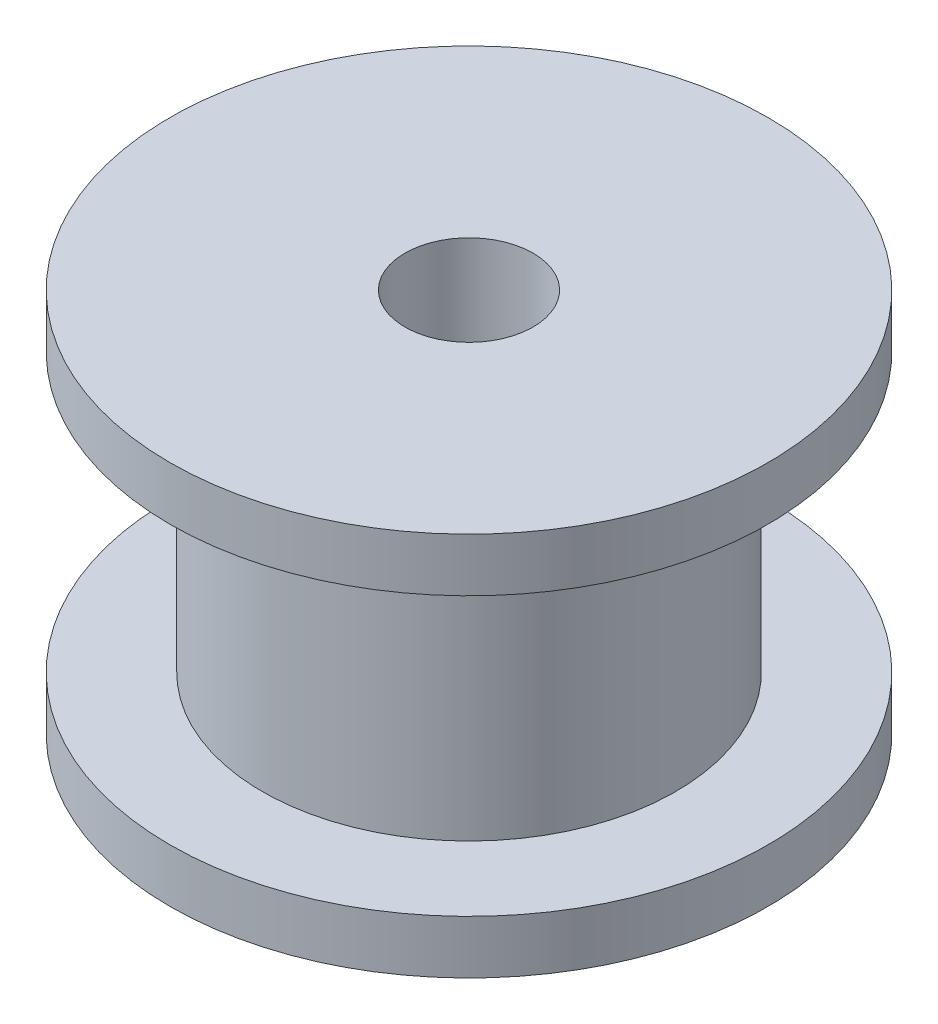
SolidWorks part; units mm, degrees
ref_plane "Plano frontal" through (0, 0, 0) normal (0, 0, 1) x (1, 0, 0)
ref_plane "Plano superior" through (0, 0, 0) normal (0, 1, 0) x (1, 0, 0)
ref_plane "Plano direito" through (0, 0, 0) normal (1, 0, 0) x (0, 0, -1)
sketch "Esboço1" plane through (0, 0, 0) normal (0, 0, 1) x (1, 0, 0)
  line L0 (1.5, 9) -> (7, 9)
  line L1 (7, 9) -> (7, 7.75)
  line L2 (7, 7.75) -> (4.84, 7.75)
  line L3 (4.84, 7.75) -> (4.84, 1.25)
  line L4 (4.84, 1.25) -> (7, 1.25)
  line L5 (7, 1.25) -> (7, 0)
  line L6 (7, 0) -> (1.5, 0)
  line L7 (1.5, 0) -> (1.5, 9)
  line L8 (0, 0) -> (0, 9.423) construction
  point P11 (0, 9.423)
  dimension "D1" = 14
  dimension "D2" = 3
  dimension "D3" = 9
  dimension "D4" = 6.5
  dimension "D5" = 9.68
revolve "Revolução1" add sketch "Esboço1" angle 360 about L8
